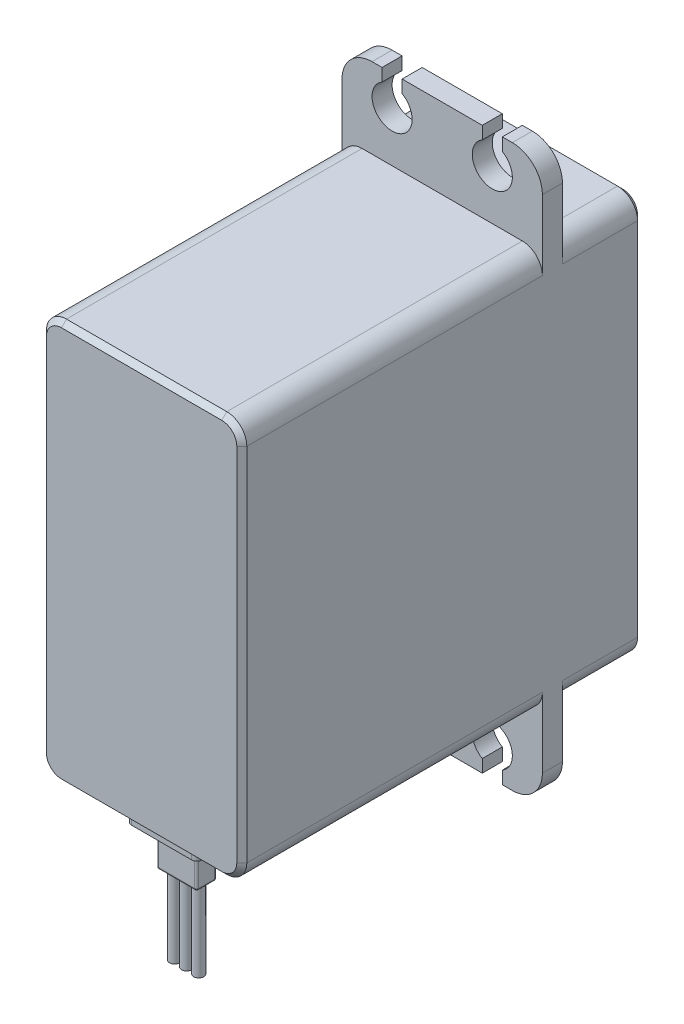
SolidWorks part; units mm, degrees
ref_plane "前视基准面" through (0, 0, 0) normal (0, 0, 1) x (1, 0, 0)
ref_plane "上视基准面" through (0, 0, 0) normal (0, 1, 0) x (1, 0, 0)
ref_plane "右视基准面" through (0, 0, 0) normal (1, 0, 0) x (0, 0, -1)
sketch "草图1" plane through (0, 0, 0) normal (0, 0, 1) x (1, 0, 0)
  line L1 (-10, -28) -> (10, -28)
  line L2 (-10, -28) -> (-10, 28)
  line L3 (-10, 28) -> (10, 28)
  line L4 (10, -28) -> (10, 28)
  line L5 (-10, -28) -> (10, 28) construction
  line L6 (-10, 28) -> (10, -28) construction
  point P0 (0, 0)
  dimension "D1" = 20
  dimension "D2" = 56
extrude "凸台-拉伸1" add sketch "草图1" along normal blind 40
sketch "草图2" plane through (0, 0, 40) normal (0, 0, 1) x (1, 0, 0)
  line L0 (10, -28) -> (10, 28) construction
  line L1 (-10, -20) -> (10, -20)
  line L2 (-10, -20) -> (-10, 20)
  line L3 (-10, 20) -> (10, 20)
  line L4 (10, -20) -> (10, 20)
  line L5 (-10, -20) -> (10, 20) construction
  line L6 (-10, 20) -> (10, -20) construction
  point P0 (0, 0)
  dimension "D1" = 40
extrude "切除-拉伸1" cut sketch "草图2" against normal blind 30 flip side to cut
extrude "切除-拉伸2" cut sketch "草图2<2>" along normal blind 8 from surface flip side to cut contours L2 L3 L4 L1 starting at face at (0, 0, 0)
sketch "草图2<2>" plane through (0, 0, 40) normal (0, 0, 1) x (1, 0, 0) same geometry as "草图2"
sketch "草图3" plane through (0, 0, 10) normal (0, 0, 1) x (1, 0, 0)
  line L0 (4, 26.7321) -> (4, 28)
  line L1 (10, 28) -> (-10, 28) construction
  line L2 (4, 28) -> (6, 28)
  line L3 (6, 28) -> (6, 26.7321)
  line L4 (5, 25) -> (5, 28) construction
  line L5 (10, 20) -> (10, 28) construction
  line L6 (-6, 26.7321) -> (-6, 28)
  line L7 (-6, 28) -> (-4, 28)
  line L8 (-4, 28) -> (-4, 26.7321)
  line L9 (0, 0) -> (15.7926, 0) construction
  line L10 (5, -25) -> (5, -28) construction
  line L11 (-4, -28) -> (-4, -26.7321)
  line L12 (-6, -28) -> (-4, -28)
  line L13 (-6, -26.7321) -> (-6, -28)
  line L14 (6, -28) -> (6, -26.7321)
  line L15 (4, -28) -> (6, -28)
  line L16 (4, -26.7321) -> (4, -28)
  arc A0 (4, 26.7321) -> (6, 26.7321) centre (5, 25) ccw
  arc A1 (-6, 26.7321) -> (-4, 26.7321) centre (-5, 25) ccw
  arc A2 (-6, -26.7321) -> (-4, -26.7321) centre (-5, -25) cw
  arc A3 (4, -26.7321) -> (6, -26.7321) centre (5, -25) cw
  dimension "D1" = 2
  dimension "D2" = 3
  dimension "D3" = 2
  dimension "D4" = 4
  dimension "D6" = 10
  dimension "D5" = 2
extrude "切除-拉伸3" cut sketch "草图3" against normal through all
sketch "草图4" plane through (0, -20, 0) normal (0, -1, 0) x (1, 0, 0)
  line L0 (-10, 40) -> (10, 40) construction
  line L1 (-3.5, 33) -> (3.5, 33)
  line L2 (-3.5, 33) -> (-3.5, 38)
  line L3 (-3.5, 38) -> (3.5, 38)
  line L4 (3.5, 33) -> (3.5, 38)
  line L5 (-3.5, 33) -> (3.5, 38) construction
  line L6 (-3.5, 38) -> (3.5, 33) construction
  point P0 (0, 35.5)
  dimension "D1" = 7
  dimension "D2" = 5
  dimension "D3" = 2
extrude "凸台-拉伸2" add sketch "草图4" along normal blind 2
sketch "草图5" plane through (0, -22, 0) normal (0, -1, 0) x (1, 0, 0)
  line L0 (-3.5, 38) -> (3.5, 33) construction
  line L1 (-2, 34.5) -> (2, 34.5)
  line L2 (-2, 34.5) -> (-2, 36.5)
  line L3 (-2, 36.5) -> (2, 36.5)
  line L4 (2, 34.5) -> (2, 36.5)
  line L5 (-2, 34.5) -> (2, 36.5) construction
  line L6 (-2, 36.5) -> (2, 34.5) construction
  line L7 (3.5, 38) -> (-3.5, 33) construction
  point P0 (0, 35.5)
  dimension "D1" = 4
  dimension "D2" = 2
extrude "凸台-拉伸3" add sketch "草图5" along normal blind 4
sketch "草图6" plane through (0, -26, 0) normal (0, -1, 0) x (1, 0, 0)
  line L0 (2, 34.5) -> (2, 36.5) construction
  line L1 (-2, 35.5) -> (2, 35.5) construction
  line L2 (-2, 36.5) -> (-2, 34.5) construction
  line L3 (2, 34.5) -> (2, 36.5) construction
  circle A0 centre (1.2, 35.5) radius 0.5
  circle A1 centre (0, 35.5) radius 0.5
  circle A2 centre (-1.2, 35.5) radius 0.5
  dimension "D1" = 1
  dimension "D2" = 0.8
  dimension "D4" = 1.2
  dimension "D3" = 1.2
extrude "凸台-拉伸4" add sketch "草图6" along normal blind 8
sketch "草图7" plane through (0, 0, 0) normal (0, 0, -1) x (-1, 0, 0)
  line L0 (-10, -20) -> (10, -20) construction
  circle A0 centre (0, -12) radius 6
  dimension "D1" = 12
  dimension "D2" = 8
extrude "凸台-拉伸5" add sketch "草图7" along normal blind 2
sketch "草图8" plane through (0, 0, -2) normal (0, 0, -1) x (-1, 0, 0)
  circle A0 centre (0, -12) radius 5
  dimension "D1" = 10
extrude "切除-拉伸4" cut sketch "草图8" against normal blind 0.8
sketch "草图9" plane through (0, 0, -1.2) normal (0, 0, -1) x (-1, 0, 0)
  circle A0 centre (0, -12) radius 2.5
  dimension "D1" = 5
extrude "切除-拉伸5" cut sketch "草图9" against normal blind 4
sketch "草图10" plane through (0, 0, 2.8) normal (0, 0, -1) x (-1, 0, 0)
  circle A1 centre (0, -12) radius 2.5
  circle A2 centre (0, -12) radius 2.5
  dimension "D1" = 0
extrude "凸台-拉伸6" add sketch "草图10" along normal blind 10 separate body
sketch "草图11" plane through (0, 0, -7.2) normal (0, 0, -1) x (-1, 0, 0)
  line L0 (0, -12) -> (0, -9.5) construction
  line L1 (0, -10) -> (-0.2796, -9.5157)
  line L2 (0, -10) -> (0.2796, -9.5157)
  line L3 (0.618, -10.0979) -> (0.5018, -9.5509)
  line L4 (0.618, -10.0979) -> (1.0336, -9.7237)
  line L5 (1.1756, -10.382) -> (1.234, -9.8258)
  line L6 (1.1756, -10.382) -> (1.6865, -10.1545)
  line L7 (1.618, -10.8244) -> (1.8455, -10.3135)
  line L8 (1.618, -10.8244) -> (2.1742, -10.766)
  line L9 (1.9021, -11.382) -> (2.2763, -10.9664)
  line L10 (1.9021, -11.382) -> (2.4491, -11.4982)
  line L11 (2, -12) -> (2.4843, -11.7204)
  line L12 (2, -12) -> (2.4843, -12.2796)
  line L13 (1.9021, -12.618) -> (2.4491, -12.5018)
  line L14 (1.9021, -12.618) -> (2.2763, -13.0336)
  line L15 (1.618, -13.1756) -> (2.1742, -13.234)
  line L16 (1.618, -13.1756) -> (1.8455, -13.6865)
  line L17 (1.1756, -13.618) -> (1.6865, -13.8455)
  line L18 (1.1756, -13.618) -> (1.234, -14.1742)
  line L19 (0.618, -13.9021) -> (1.0336, -14.2763)
  line L20 (0.618, -13.9021) -> (0.5018, -14.4491)
  line L21 (0, -14) -> (0.2796, -14.4843)
  line L22 (0, -14) -> (-0.2796, -14.4843)
  line L23 (-0.618, -13.9021) -> (-0.5018, -14.4491)
  line L24 (-0.618, -13.9021) -> (-1.0336, -14.2763)
  line L25 (-1.1756, -13.618) -> (-1.234, -14.1742)
  line L26 (-1.1756, -13.618) -> (-1.6865, -13.8455)
  line L27 (-1.618, -13.1756) -> (-1.8455, -13.6865)
  line L28 (-1.618, -13.1756) -> (-2.1742, -13.234)
  line L29 (-1.9021, -12.618) -> (-2.2763, -13.0336)
  line L30 (-1.9021, -12.618) -> (-2.4491, -12.5018)
  line L31 (-2, -12) -> (-2.4843, -12.2796)
  line L32 (-2, -12) -> (-2.4843, -11.7204)
  line L33 (-1.9021, -11.382) -> (-2.4491, -11.4982)
  line L34 (-1.9021, -11.382) -> (-2.2763, -10.9664)
  line L35 (-1.618, -10.8244) -> (-2.1742, -10.766)
  line L36 (-1.618, -10.8244) -> (-1.8455, -10.3135)
  line L37 (-1.1756, -10.382) -> (-1.6865, -10.1545)
  line L38 (-1.1756, -10.382) -> (-1.234, -9.8258)
  line L39 (-0.618, -10.0979) -> (-1.0336, -9.7237)
  line L40 (-0.618, -10.0979) -> (-0.5018, -9.5509)
  circle A0 centre (0, -12) radius 2.5 construction
  arc A1 (0.2796, -9.5157) -> (-0.2796, -9.5157) centre (0, -12) ccw
  arc A2 (1.0336, -9.7237) -> (0.5018, -9.5509) centre (0, -12) ccw
  arc A3 (1.6865, -10.1545) -> (1.234, -9.8258) centre (0, -12) ccw
  arc A4 (2.1742, -10.766) -> (1.8455, -10.3135) centre (0, -12) ccw
  arc A5 (2.4491, -11.4982) -> (2.2763, -10.9664) centre (0, -12) ccw
  arc A6 (2.4843, -12.2796) -> (2.4843, -11.7204) centre (0, -12) ccw
  arc A7 (2.2763, -13.0336) -> (2.4491, -12.5018) centre (0, -12) ccw
  arc A8 (1.8455, -13.6865) -> (2.1742, -13.234) centre (0, -12) ccw
  arc A9 (1.234, -14.1742) -> (1.6865, -13.8455) centre (0, -12) ccw
  arc A10 (0.5018, -14.4491) -> (1.0336, -14.2763) centre (0, -12) ccw
  arc A11 (-0.2796, -14.4843) -> (0.2796, -14.4843) centre (0, -12) ccw
  arc A12 (-1.0336, -14.2763) -> (-0.5018, -14.4491) centre (0, -12) ccw
  arc A13 (-1.6865, -13.8455) -> (-1.234, -14.1742) centre (0, -12) ccw
  arc A14 (-2.1742, -13.234) -> (-1.8455, -13.6865) centre (0, -12) ccw
  arc A15 (-2.4491, -12.5018) -> (-2.2763, -13.0336) centre (0, -12) ccw
  arc A16 (-2.4843, -11.7204) -> (-2.4843, -12.2796) centre (0, -12) ccw
  arc A17 (-2.2763, -10.9664) -> (-2.4491, -11.4982) centre (0, -12) ccw
  arc A18 (-1.8455, -10.3135) -> (-2.1742, -10.766) centre (0, -12) ccw
  arc A19 (-1.234, -9.8258) -> (-1.6865, -10.1545) centre (0, -12) ccw
  arc A20 (-0.5018, -9.5509) -> (-1.0336, -9.7237) centre (0, -12) ccw
  point P66 (0, -12)
  dimension "D1" = 2
  dimension "D2" = 60
  dimension "D3" = 20
extrude "切除-拉伸6" cut sketch "草图11" against normal through all
sketch "草图12" plane through (0, 0, 0) normal (1, 0, 0) x (0, 0, -1)
  line L0 (7.2, -10) -> (7.2, -8)
  line L1 (7.2, -10.382) -> (7.2, -9.8258) construction
  line L2 (7.2, -8) -> (6.0453, -8)
  line L3 (6.0453, -8) -> (7.2, -10)
  dimension "D1" = 30
  dimension "D2" = 2
revolve "切除-旋转1" cut sketch "草图12" angle 360 about axis through (0, -12, -7.2) along (0, 0, 1)
ref_plane "基准面1" through (0, 0, -2.2) normal (0, 0, 1) x (1, 0, 0)
mirror "镜向1" about plane through (0, 0, -2.2) normal (0, 0, 1) of "切除-旋转1"
hole_wizard "M2 螺纹孔1" positions "3D草图1" profile "草图13" tap size "M2" standard "GB"
sketch3d "3D草图1"
  arc A0 (0.618, -13.9021, -7.2) -> (0, -14, -7.2) centre (0, -12, -7.2) ccw construction
  point P0 (0, -12, -7.2)
  point P7 (0, -12, -9.2)
sketch "草图13" plane through (0, -12, -7.2) normal (1, 0, 0) x (0, 1, 0)
  line L0 (0, 0) -> (0, 10.4807)
  line L1 (0, 10.4807) -> (0.8, 10)
  line L2 (0.8, 10) -> (0.8, 0)
  line L5 (0.8, 0) -> (0, 0)
  line L10 (0, 10.4807) -> (-0.8, 10) construction
  line L11 (0, -6.35) -> (0, 107.95) construction
  dimension "螺纹孔钻头直径" = 1.6
  dimension "螺纹孔钻头深度" = 10
  dimension "导头角度" = 118
cosmetic thread "孔螺蚊线1" parameters "D1"=4, "D2"=2
fillet "圆角1" radius 3 4 edges at (-10, -28, 9) (10, -28, 9) (-10, 28, 9) (10, 28, 9)
fillet "圆角2" radius 2 8 edges at (-10, 20, 4) (-10, -20, 4) (10, -20, 4) (10, 20, 4) (-10, -20, 25) (-10, 20, 25) (10, -20, 25) (10, 20, 25)
fillet "圆角3" radius 0.5 4 edges at (3.5, -21, 33) (-3.5, -21, 33) (-3.5, -21, 38) (3.5, -21, 38)
fillet "圆角4" radius 0.2 8 edges at (2, -26, 35.5) (0, -26, 36.5) (-2, -26, 35.5) (0, -26, 34.5) (2, -24, 34.5) (-2, -24, 34.5) (-2, -24, 36.5) (2, -24, 36.5)
chamfer "倒角1" distance 0.5 angle 45 17 edges at (-6, -12, -2) (-10, 0, 0) (-9.4142, -19.4142, 0) (-9.4142, 19.4142, 0) (0, -20, 0) (0, 20, 0) (9.4142, -19.4142, 0) (9.4142, 19.4142, 0) (10, 0, 0) (0, -20, 40) (9.4142, -19.4142, 40) (-9.4142, -19.4142, 40) (10, 0, 40) (-10, 0, 40) (9.4142, 19.4142, 40) (-9.4142, 19.4142, 40) (0, 20, 40)
move or copy body "实体-移动/复制1" [suppressed] bodies to move or copy 120 121
move or copy body "实体-移动/复制2" [suppressed] bodies to move or copy 122 123 parameters "D1"=0, "D2"=0, "D3"=0
move or copy body "实体-移动/复制3" [suppressed] bodies to move or copy 124 125 parameters "D1"=0, "D2"=0, "D3"=0
move or copy body "实体-移动/复制4" [suppressed] bodies to move or copy 126 127 parameters "D1"=0, "D2"=0, "D3"=0
move or copy body "实体-移动/复制5" [suppressed] bodies to move or copy 128 129 parameters "D1"=0, "D2"=0, "D3"=0
equation "\"0。8\"=0.715841"
